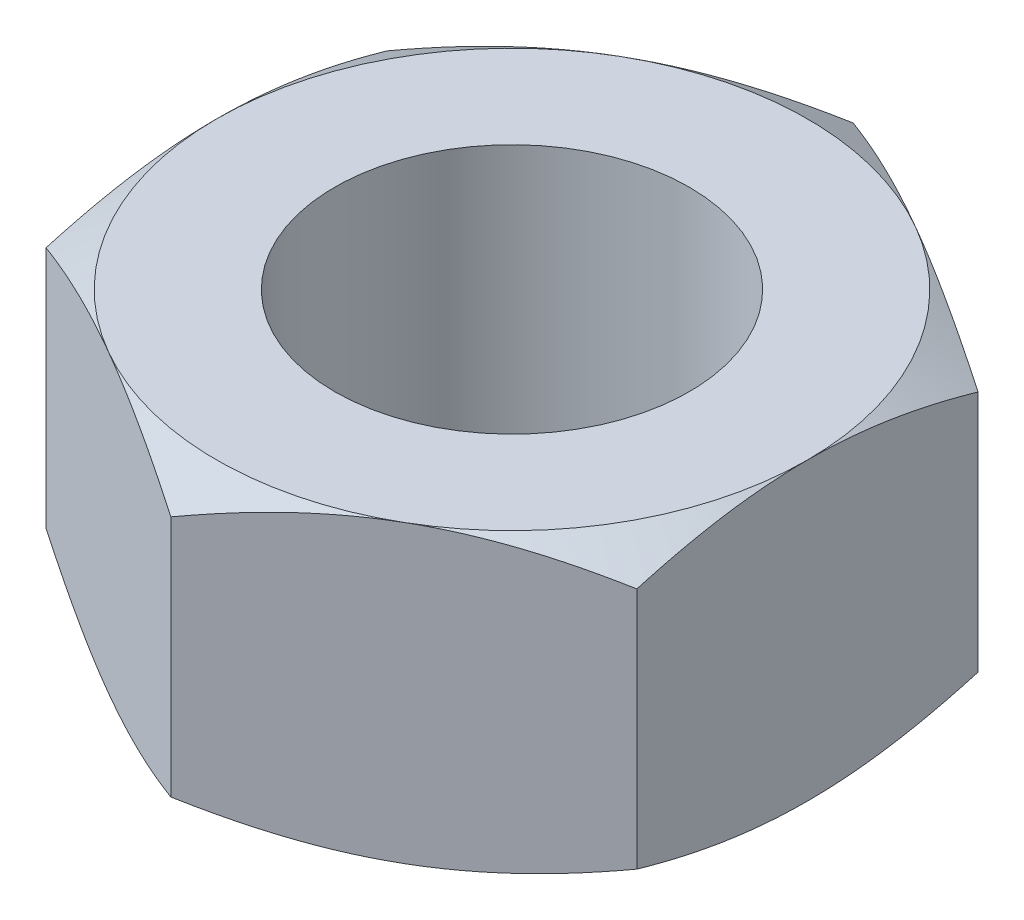
SolidWorks part; units mm, degrees
material "Alloy Steel"
ref_plane "Front Plane" through (0, 0, 0) normal (0, 0, 1) x (1, 0, 0)
ref_plane "Top Plane" through (0, 0, 0) normal (0, 1, 0) x (1, 0, 0)
ref_plane "Right Plane" through (0, 0, 0) normal (1, 0, 0) x (0, 0, -1)
sketch "Sketch1" plane through (0, 0, 0) normal (0, 1, 0) x (1, 0, 0)
  line L1 (-5, 2.8868) -> (-5, -2.8868)
  line L2 (-5, -2.8868) -> (0, -5.7735)
  line L3 (0, -5.7735) -> (5, -2.8868)
  line L4 (5, -2.8868) -> (5, 2.8868)
  line L5 (5, 2.8868) -> (0, 5.7735)
  line L6 (0, 5.7735) -> (-5, 2.8868)
  circle A0 centre (0, 0) radius 5 construction
  circle A1 centre (0, 0) radius 3
  dimension "Thread Size" = 6
  dimension "Hex" = 10
extrude "Boss-Extrude1" add sketch "Sketch1" along normal mid plane 5
sketch "Sketch2" plane through (0, 2.5, 0) normal (0, 1, 0) x (1, 0, 0)
  circle A0 centre (0, 0) radius 3 construction
  circle A1 centre (0, 0) radius 3
curve "Helix/Spiral1" pitch 1 height 6 turns 6 parameters "Pitch"=1
sketch "Sketch5" plane through (0, 2.5, 0) normal (0, 1, 0) x (1, 0, 0)
  circle A0 centre (0, 0) radius 5 construction
  circle A1 centre (0, 0) radius 5
extrude "Cut-Extrude2" cut sketch "Sketch5" against normal through all draft 60 flip side to cut
mirror "Mirror1" about plane through (0, 0, 0) normal (0, 1, 0) of "Cut-Extrude2"
ref_axis "Axis1" through (0, 2.5, 0) along (0, -1, 0)
sketch "Sketch3" [suppressed] plane through (0, 0, 0) normal (1, 0, 0) x (0, 0, -1)
  line L0 (2.3505, 3) -> (3, 3.375)
  line L1 (3, 3.375) -> (3, 2.5)
  line L2 (3, 2.5) -> (2.3505, 2.875)
  line L3 (2.3505, 2.875) -> (2.3505, 3)
  line L4 (2.6752, 3.1875) -> (2.6752, 2.6875) construction
  line L5 (2.3505, 2.9375) -> (3, 2.9375) construction
  line L6 (3, 2.5) -> (-3, 2.5) construction
  dimension "D1" = 60
  dimension "D2" = 0.125
  dimension "D3" = 0.5
sweep "Sweep1" [suppressed] add profiles "Sketch3" path "Helix/Spiral1"
sketch "Sketch4" [suppressed] plane through (0, 2.5, 0) normal (0, 1, 0) x (1, 0, 0)
  circle A1 centre (0, 0) radius 3
  circle A2 centre (0, 0) radius 3
  dimension "D1" = 0
extrude "Cut-Extrude1" [suppressed] cut sketch "Sketch4" along normal through all and the other way through all draft 45
sketch "Sketch8" [suppressed] plane through (0, -2.5, 0) normal (0, -1, 0) x (1, 0, 0)
  circle A0 centre (0, 0) radius 3
  arc A1 (0, -3) -> (-2.1213, -2.1213) centre (0, 0) ccw construction
extrude "Cut-Extrude3" [suppressed] cut sketch "Sketch8" along normal through all and the other way through all draft 45
equation "\"D2@Sketch3\" = \"Pitch@Helix/Spiral1\"*.125"
equation "\"D3@Sketch3\" = \"Pitch@Helix/Spiral1\"*.5"
equation "\"D3@Helix/Spiral1\" = \"Height@Boss-Extrude1\"+\"Pitch@Helix/Spiral1\""
